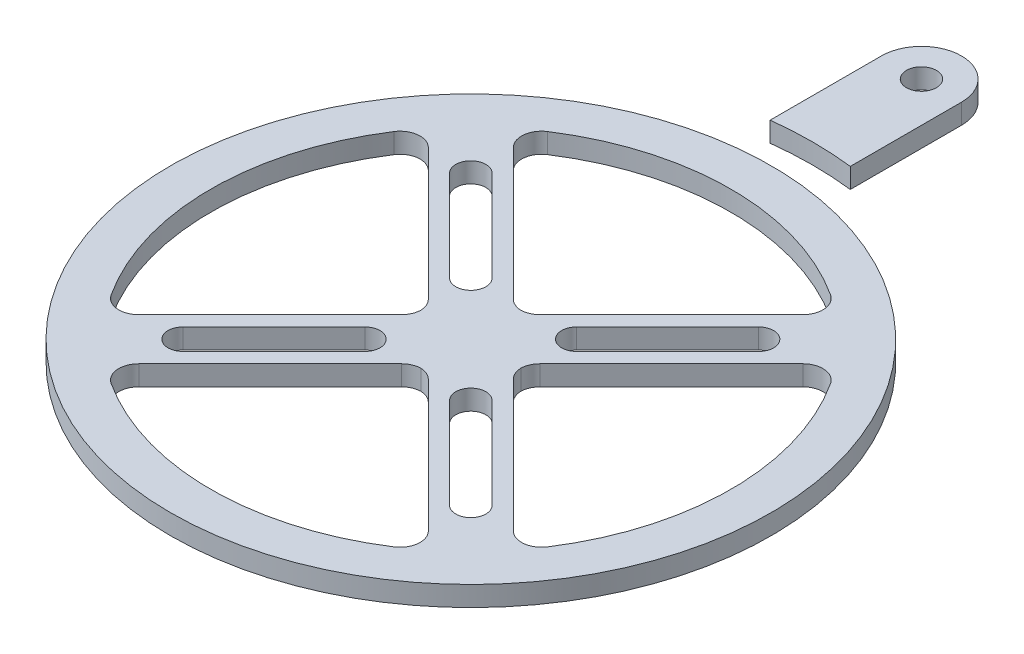
SolidWorks part; units mm, degrees
ref_plane "Front Plane" through (0, 0, 0) normal (0, 0, 1) x (1, 0, 0)
ref_plane "Top Plane" through (0, 0, 0) normal (0, 1, 0) x (1, 0, 0)
ref_plane "Right Plane" through (0, 0, 0) normal (1, 0, 0) x (0, 0, -1)
sketch "Sketch1" plane through (0, 0, 0) normal (0, 1, 0) x (1, 0, 0)
  circle A0 centre (0, 0) radius 30
  dimension "D1" = 60
extrude "Boss-Extrude1" add sketch "Sketch1" along normal blind 2
sketch "Sketch2" plane through (0, 0, 0) normal (0, 1, 0) x (1, 0, 0)
  line L0 (0, 0) -> (0, 48.4262) construction
  line L1 (-4, 33.8932) -> (-4, 45)
  line L2 (4, 45) -> (4, 33.8932)
  circle A0 centre (0, 0) radius 45 construction
  circle A1 centre (0, 45) radius 1.5
  arc A2 (-4, 45) -> (4, 45) centre (0, 45) cw
  arc A3 (4, 33.8932) -> (-4, 33.8932) centre (0, 0) ccw
  point P6 (4, 33.8932)
  point P10 (0, 0)
  point P12 (0, 0)
  dimension "D1" = 90
  dimension "D2" = 3
  dimension "D3" = 4
extrude "Boss-Extrude2" add sketch "Sketch2" along normal blind 2 separate body
sketch "Sketch3" plane through (0, 0, 0) normal (0, -1, 0) x (1, 0, 0)
  line L0 (0, 0) -> (32.3878, 32.3878) construction
  line L1 (0, 0) -> (-32.5154, 32.5154) construction
  line L2 (0, 0) -> (69.9427, 0) construction
  line L3 (69.9427, 0) -> (61.7718, -9.7724) construction
  line L4 (61.7718, -9.7724) -> (61.9897, -9.7724) construction
  line L5 (-16.121, 20.3636) -> (-0.7071, 4.9497)
  line L6 (0.7071, 4.9497) -> (16.121, 20.3636)
  line L7 (5.2869, 5.2869) -> (14.3692, 14.3692) construction
  line L8 (4.2263, 6.3476) -> (13.3086, 15.4299)
  line L9 (6.3476, 4.2263) -> (15.4299, 13.3086)
  arc A0 (-0.7071, 4.9497) -> (0.7071, 4.9497) centre (0, 0) cw
  arc A1 (16.121, 20.3636) -> (-16.121, 20.3636) centre (0, 0) ccw
  arc A2 (4.2263, 6.3476) -> (6.3476, 4.2263) centre (5.2869, 5.2869) ccw
  arc A3 (15.4299, 13.3086) -> (13.3086, 15.4299) centre (14.3692, 14.3692) ccw
  point P9 (9.8281, 9.8281)
  dimension "D5" = 5
  dimension "D6" = 1.5
  dimension "D1" = 90
  dimension "D2" = 45
  dimension "D3" = 3
  dimension "D4" = 3
extrude "Cut-Extrude1" cut sketch "Sketch3" against normal blind 2
fillet "Fillet1" radius 2 4 edges at (16.121, 1, 20.3636) (-16.121, 1, 20.3636) (-0.7071, 1, 4.9497) (0.7071, 1, 4.9497)
pattern_circular "CirPattern3" count 4 over 360 about axis through (0, 2, 0) along (0, -1, 0) of "Cut-Extrude1", "Fillet1"
